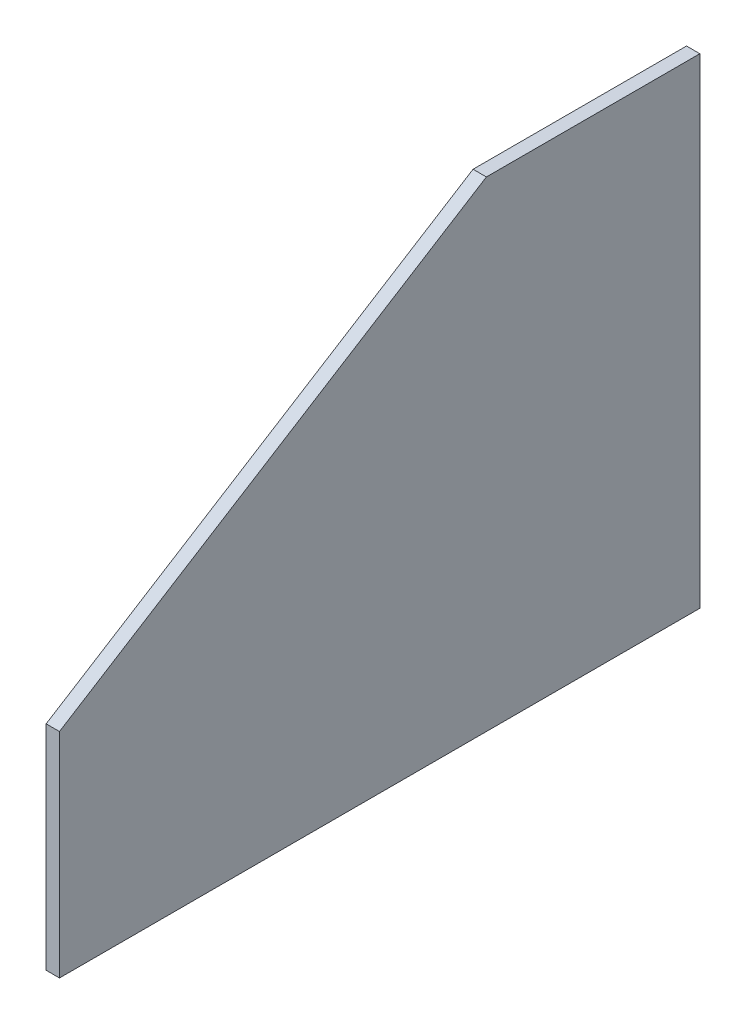
SolidWorks part; units mm, degrees
ref_plane "Front Plane" through (0, 0, 0) normal (0, 0, 1) x (1, 0, 0)
ref_plane "Top Plane" through (0, 0, 0) normal (0, 1, 0) x (1, 0, 0)
ref_plane "Right Plane" through (0, 0, 0) normal (1, 0, 0) x (0, 0, -1)
sketch "Sketch1" plane through (0, 0, 0) normal (1, 0, 0) x (0, 0, -1)
  line L0 (0, 0) -> (0, 114.3)
  line L1 (0, 114.3) -> (-50.8, 114.3)
  line L2 (-50.8, 114.3) -> (-152.4, 50.8)
  line L3 (-152.4, 50.8) -> (-152.4, 0)
  line L4 (-152.4, 0) -> (0, 0)
  dimension "D1" = 50.8
  dimension "D2" = 114.3
  dimension "D3" = 152.4
extrude "Boss-Extrude1" add sketch "Sketch1" along normal blind 3.175
